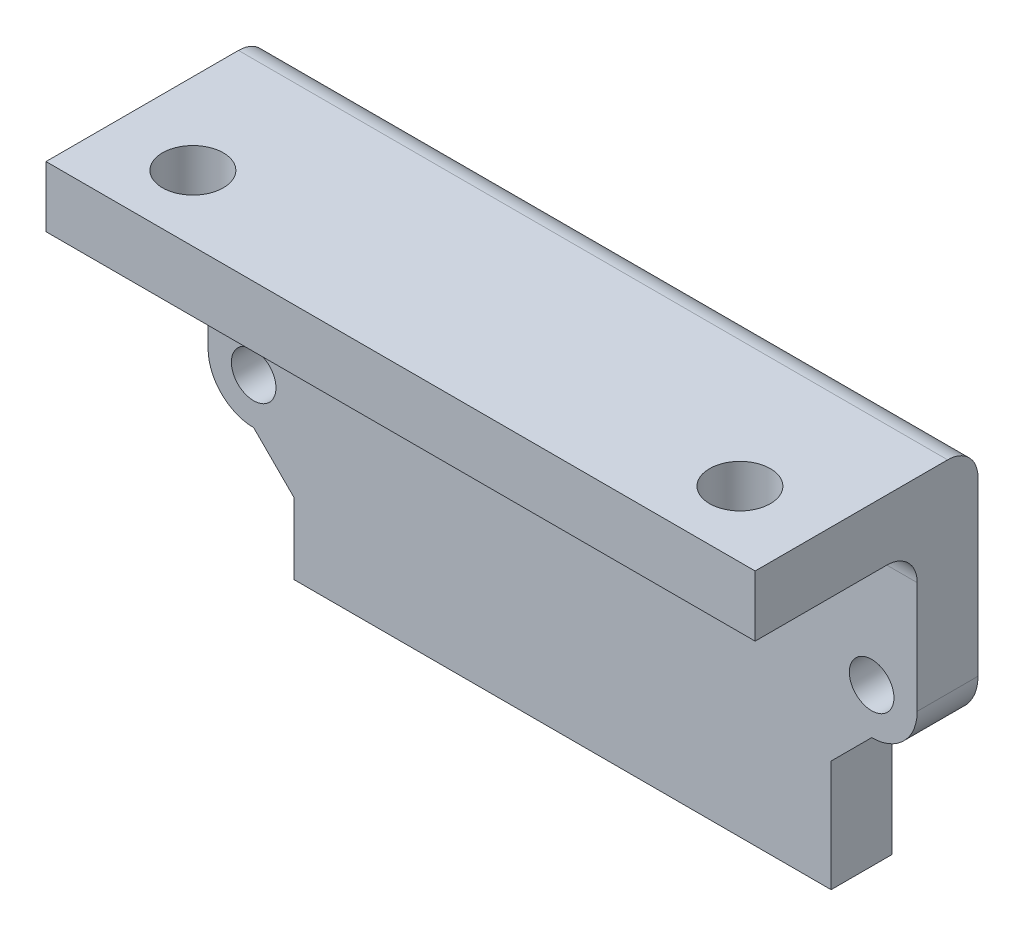
SolidWorks part; units mm, degrees
ref_plane "前视基准面" through (0, 0, 0) normal (0, 0, 1) x (1, 0, 0)
ref_plane "上视基准面" through (0, 0, 0) normal (0, 1, 0) x (1, 0, 0)
ref_plane "右视基准面" through (0, 0, 0) normal (1, 0, 0) x (0, 0, -1)
sketch "草图1" plane through (0, 0, 0) normal (0, 0, 1) x (1, 0, 0)
  line L1 (-13.25, -8.125) -> (13.25, -8.125)
  line L2 (-13.25, -8.125) -> (-13.25, -4.625)
  line L3 (-13.25, 8.625) -> (13.25, 8.625)
  line L4 (13.25, -8.125) -> (13.25, -2.625)
  line L9 (-17.5, -0.375) -> (-17.5, 8.625)
  line L10 (-17.5, 8.625) -> (-13.25, 8.625)
  line L11 (17.5, 1.625) -> (17.5, 8.625)
  line L12 (13.25, 8.625) -> (17.5, 8.625)
  line L13 (-15.25, -2.625) -> (-13.25, -4.625)
  line L14 (15.25, -0.625) -> (13.25, -2.625)
  circle A0 centre (-15.25, -0.375) radius 1.1
  circle A1 centre (15.25, 1.625) radius 1.1
  arc A2 (-17.5, -0.375) -> (-15.25, -2.625) centre (-15.25, -0.375) ccw
  arc A3 (15.25, -0.625) -> (17.5, 1.625) centre (15.25, 1.625) ccw
  point P0 (0, 0)
  point P7 (0, 0)
  point P9 (0, 0)
  point P12 (0, 0)
  point P14 (0, 0)
extrude "凸台-拉伸1" add sketch "草图1" along normal blind 3
sketch "草图2" plane through (0, 8.625, 0) normal (0, 1, 0) x (1, 0, 0)
  line L0 (17.5, 0) -> (-17.5, 0)
  line L1 (-17.5, 0) -> (-17.5, -11)
  line L2 (-17.5, -11) -> (17.5, -11)
  line L3 (17.5, -11) -> (17.5, 0)
extrude "凸台-拉伸2" add sketch "草图2" along normal blind 3
fillet "圆角1" radius 1.5 2 edges at (0, 8.625, 3) (0, 11.625, 0)
sketch "草图3" plane through (0, 8.625, 0) normal (0, -1, 0) x (1, 0, 0)
  circle A0 centre (13.5, 7.75) radius 1.5
  circle A1 centre (-13.5, 7.75) radius 1.5
extrude "切除-拉伸1" cut sketch "草图3" against normal blind 3
